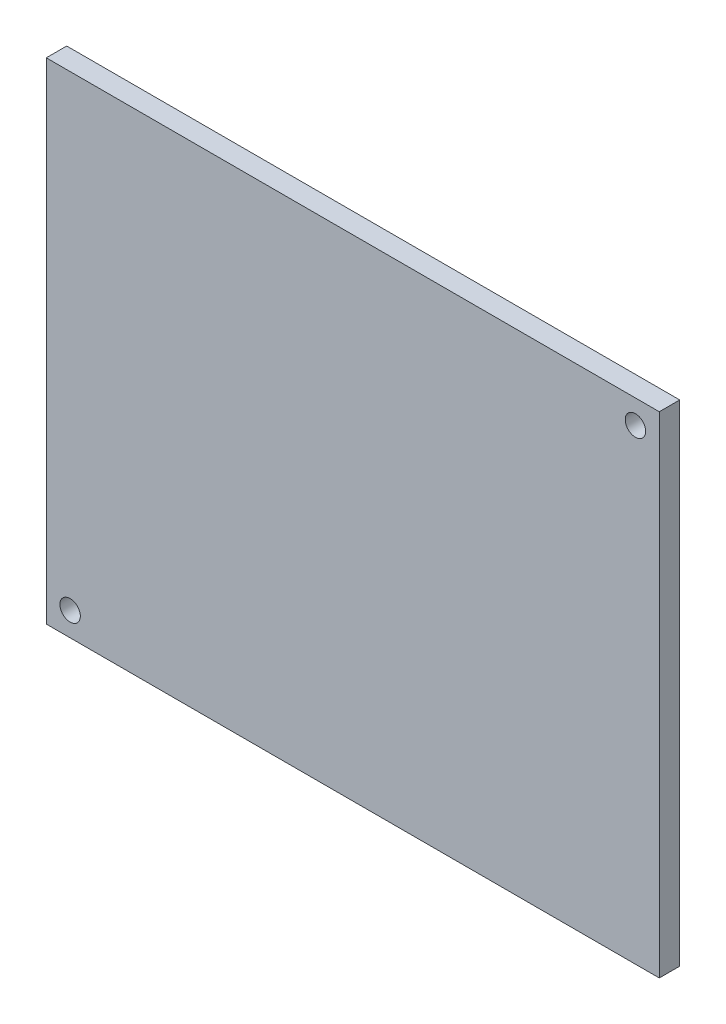
SolidWorks part; units mm, degrees
ref_plane "Alzado" through (0, 0, 0) normal (0, 0, 1) x (1, 0, 0)
ref_plane "Planta" through (0, 0, 0) normal (0, 1, 0) x (1, 0, 0)
ref_plane "Vista lateral" through (0, 0, 0) normal (1, 0, 0) x (0, 0, -1)
sketch "Croquis1" plane through (0, 0, 0) normal (0, 0, 1) x (1, 0, 0)
  line L5 (-45, -36) -> (45, -36)
  line L6 (-45, -36) -> (-45, 36)
  line L19 (-45, 36) -> (45, 36)
  line L24 (45, -36) -> (45, 36)
  line L25 (-45, -36) -> (45, 36) construction
  line L26 (-45, 36) -> (45, -36) construction
  point P0 (0, 0)
  dimension "D1" = 90
  dimension "D2" = 72
extrude "Saliente-Extruir2" add sketch "Croquis1" against normal blind 3 contours L5 region at (0, 0, 0)
sketch "Croquis2" plane through (0, 0, 0) normal (0, 0, 1) x (1, 0, 0)
  line L4 (-45, -36) -> (45, -36)
  line L5 (45, -36) -> (45, 36)
  line L6 (45, 36) -> (-45, 36)
  line L7 (-45, 36) -> (-45, -36)
  line L8 (-45, -36) -> (45, -36)
  line L9 (45, -36) -> (45, 36)
  line L10 (45, 36) -> (-45, 36)
  line L11 (-45, 36) -> (-45, -36)
  circle A0 centre (-41.5, -32.5) radius 1.5 construction
  circle A1 centre (41.5, 32.5) radius 1.5 construction
  circle A2 centre (-41.5, -32.5) radius 1.5
  circle A3 centre (41.5, 32.5) radius 1.5
  dimension "D1" = 0
extrude "Cortar-Extruir1" cut sketch "Croquis2" against normal through all flip side to cut
